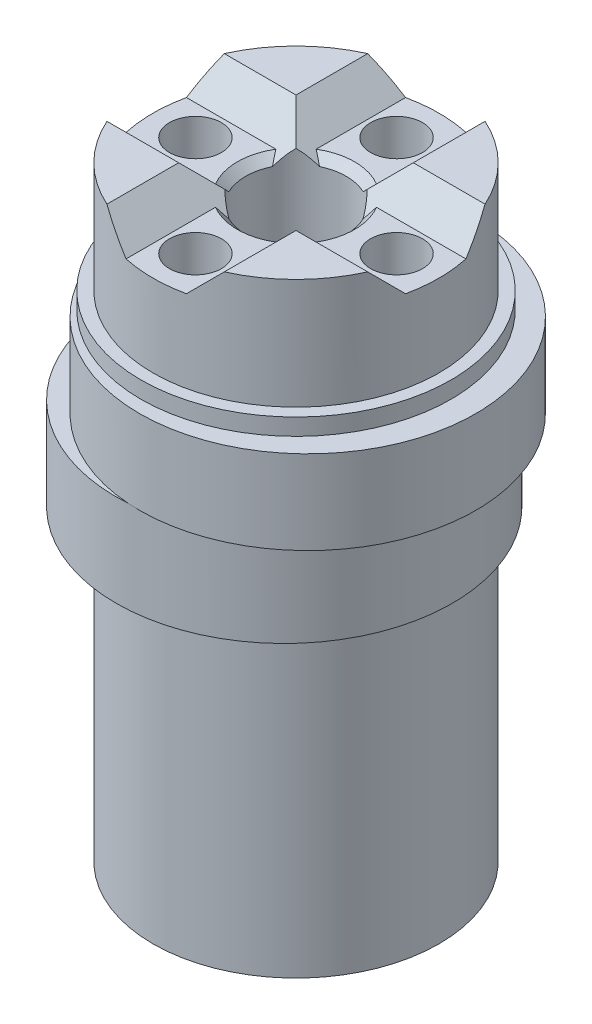
SolidWorks part; units mm, degrees
material "Like ABS"
ref_plane "Front Plane" through (0, 0, 0) normal (0, 0, 1) x (1, 0, 0)
ref_plane "Top Plane" through (0, 0, 0) normal (0, 1, 0) x (1, 0, 0)
ref_plane "Right Plane" through (0, 0, 0) normal (1, 0, 0) x (0, 0, -1)
sketch "Sketch1" plane through (0, 0, 0) normal (0, 1, 0) x (1, 0, 0)
  circle A0 centre (0, 0) radius 10.03
  dimension "D1" = 20.06
extrude "Boss-Extrude11" add sketch "Sketch1" along normal blind 5.5
sketch "Sketch20" plane through (0, 5.5, 0) normal (0, 1, 0) x (1, 0, 0)
  line L0 (0, 0) -> (1.4, 0) construction
  circle A0 centre (1.4, 0) radius 10.03
  dimension "D2" = 20.06
  dimension "D1" = 1.4
extrude "Boss-Extrude12" add sketch "Sketch20" along normal blind 5
sketch "Sketch21" plane through (0, 10.5, 0) normal (0, 1, 0) x (1, 0, 0)
  line L0 (0, 0) -> (0.7, 0) construction
  circle A0 centre (0.7, 0) radius 9.25
  dimension "D2" = 18.5
  dimension "D1" = 0.7
extrude "Boss-Extrude13" add sketch "Sketch21" along normal blind 1
sketch "Sketch22" plane through (0, 11.5, 0) normal (0, 1, 0) x (1, 0, 0)
  line L0 (0, 0) -> (0.7, 0) construction
  circle A0 centre (0.7, 0) radius 8.53
  dimension "D2" = 17.06
  dimension "D1" = 0.7
extrude "Boss-Extrude14" add sketch "Sketch22" along normal blind 6.6
sketch "Sketch30" plane through (0, 0, 0) normal (0, -1, 0) x (1, 0, 0)
  line L0 (0, 0) -> (0.7, 0) construction
  circle A1 centre (0.7, 0) radius 8.53
  dimension "D1" = 0.7
  dimension "D2" = 17.06
extrude "Boss-Extrude15" add sketch "Sketch30" along normal blind 18
sketch "Sketch31" plane through (0, 18.1, 0) normal (0, 1, 0) x (1, 0, 0)
  line L0 (0, 0) -> (0.7, 0) construction
  line L1 (0.7, 0) -> (6.7, 0) construction
  circle A0 centre (6.7, 0) radius 1.55
  dimension "D3" = 3.1
  dimension "D1" = 0.7
  dimension "D2" = 6
extrude "Cut-Extrude12" cut sketch "Sketch31" against normal up to surface (36.1 mm away) up to face at (0.7, -18, -8.53)
sketch "Sketch33" plane through (0, -18, 0) normal (0, -1, 0) x (1, 0, 0)
  line L0 (0, 0) -> (0.7, 0) construction
  circle A0 centre (0.7, 0) radius 2.1
  dimension "D2" = 4.2
  dimension "D1" = 0.7
extrude "Cut-Extrude14" cut sketch "Sketch33" against normal blind 5.8
sketch "Sketch36" plane through (0, 18.1, 0) normal (0, 1, 0) x (1, 0, 0)
  circle A0 centre (0.7, 0) radius 3
  dimension "D1" = 6
extrude "Cut-Extrude18" cut sketch "Sketch36" against normal up to surface (30.3 mm away) up to face at (0.7, -12.2, -2.1)
sketch "Sketch37" plane through (0, 18.1, 0) normal (0, 1, 0) x (1, 0, 0)
  line L0 (0.7, 2.1) -> (0.7, -2.1) construction
  line L1 (10.2, 3.5) -> (0.7, 3.5)
  line L2 (10.2, 3.5) -> (10.2, -3.5)
  line L3 (10.2, -3.5) -> (0.7, -3.5)
  line L4 (0.7, 3.5) -> (0.7, -3.5)
  circle A1 centre (0.7, 0) radius 2.1 construction
  point P12 (0.7, 0)
extrude "Cut-Extrude19" cut sketch "Sketch37" against normal blind 1.7
pattern_circular "CirPattern1" count 4 over 360 about axis through (0.7, 0, 0) along (0, 1, 0) of "Cut-Extrude19", "Cut-Extrude12"
chamfer "Chamfer1" distance 1.7 angle 45 20 edges at (8.4789, 17.25, 3.5) (8.4789, 17.25, -3.5) (6.3394, 16.4, -3.5) (6.3394, 16.4, 3.5) (-2.8, 17.25, -7.7789) (-2.8, 16.4, -5.6394) (-4.9394, 16.4, -3.5) (-7.0789, 17.25, -3.5) (-2.8, 17.25, -3.5) (-7.0789, 17.25, 3.5) (-4.9394, 16.4, 3.5) (-2.8, 16.4, 5.6394) (-2.8, 17.25, 7.7789) (-2.8, 17.25, 3.5) (4.2, 17.25, 7.7789) (4.2, 16.4, 5.6394) (4.2, 17.25, 3.5) (4.2, 16.4, -5.6394) (4.2, 17.25, -7.7789) (4.2, 17.25, -3.5)
chamfer "Chamfer2" distance 0.5 angle 45 4 edges at (3.7, 16.4, 0) (0.7, 16.4, 3) (-2.3, 16.4, 0) (0.7, 16.4, -3)
